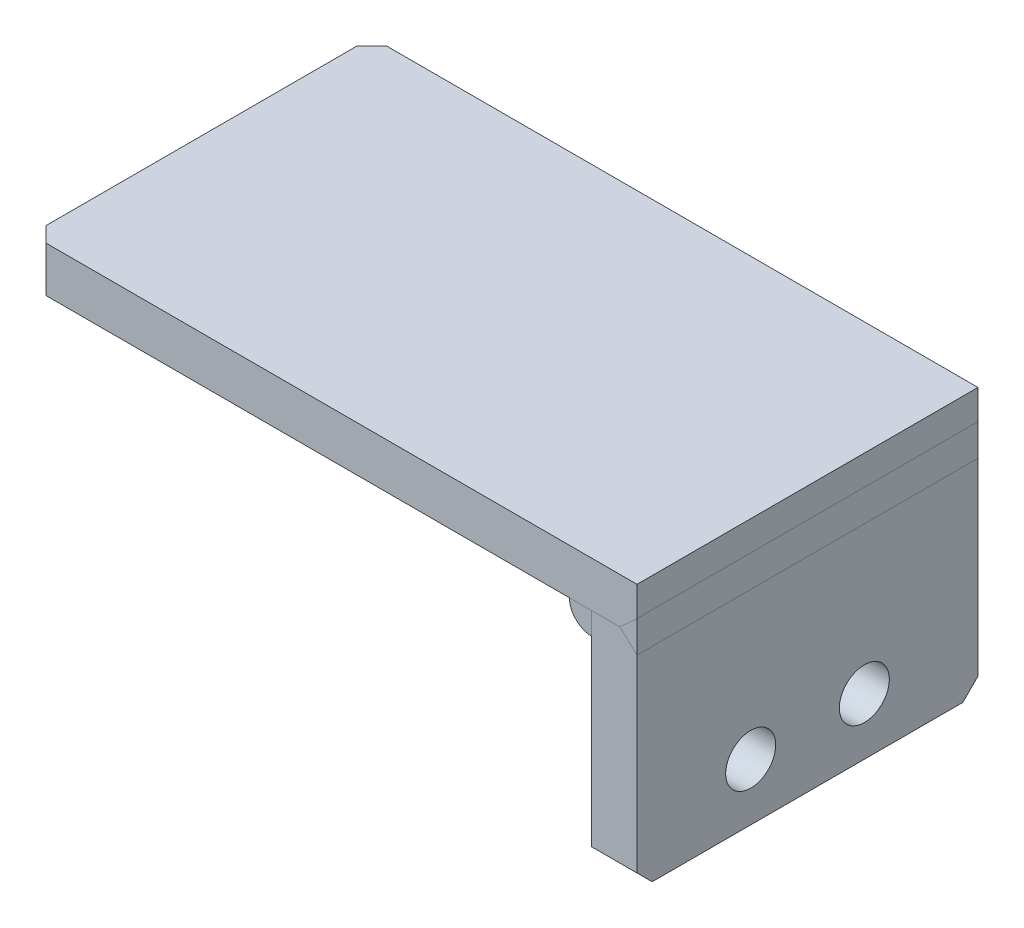
SolidWorks part; units mm, degrees
ref_plane "Front Plane" through (0, 0, 0) normal (0, 0, 1) x (1, 0, 0)
ref_plane "Top Plane" through (0, 0, 0) normal (0, 1, 0) x (1, 0, 0)
ref_plane "Right Plane" through (0, 0, 0) normal (1, 0, 0) x (0, 0, -1)
sketch "Sketch1" plane through (0, 0, 0) normal (0, 1, 0) x (1, 0, 0)
  line L1 (0, 0) -> (80, 0)
  line L2 (0, 0) -> (0, 45)
  line L3 (0, 45) -> (80, 45)
  line L4 (80, 0) -> (80, 45)
  point P4 (0, 0)
  dimension "D1" = 45
  dimension "D2" = 80
extrude "Boss-Extrude1" add sketch "Sketch1" against normal blind 6
chamfer "Chamfer1" distance 2 angle 45 2 edges at (0, -3, 0) (0, -3, -45)
sketch "Sketch2" plane through (0, -6, 0) normal (0, -1, 0) x (1, 0, 0)
  line L0 (80, -45) -> (2, -45) construction
  line L1 (80, 0) -> (74, 0)
  line L2 (80, 0) -> (80, -45)
  line L3 (80, -45) -> (74, -45)
  line L4 (74, 0) -> (74, -45)
  line L5 (2, 0) -> (80, 0) construction
  point P4 (0, 0)
  point P6 (0, 0)
  point P7 (0, 0)
  point P10 (0, 0)
  point P13 (72.2421, -43.4733)
  point P14 (0, 0)
  point P16 (65.5383, -45)
  dimension "D1" = 6
extrude "Boss-Extrude2" add sketch "Sketch2" along normal blind 29 separate body
sketch "Sketch4" plane through (0, 0, 0) normal (0, 0, 1) x (1, 0, 0)
  line L0 (74, -8.9199) -> (74, -6)
  line L1 (71.0801, -6) -> (74, -6)
  line L2 (80, -3.9063) -> (80, -8.0852)
  line L3 (80, -8.0852) -> (77.7328, -6)
  line L4 (77.7328, -6) -> (80, -3.9063)
  arc A0 (71.0801, -6) -> (74, -8.9199) centre (74, -6) ccw
  point P3 (78.4213, -6)
  point P5 (74, -7.4599)
  point P8 (72.5401, -6)
  point P9 (0, 0)
  point P11 (0, 0)
  point P12 (77.7328, -6)
extrude "Cut-Extrude1" cut sketch "Sketch4" against normal through all
extrude "Boss-Extrude3" add sketch "Sketch4<2>" against normal through all separate body
sketch "Sketch4<2>" plane through (0, 0, 0) normal (0, 0, 1) x (1, 0, 0) same geometry as "Sketch4"
sketch "Sketch6" plane through (80, 0, 0) normal (1, 0, 0) x (0, 0, -1)
  line L0 (0, 0) -> (45, 0) construction
  line L2 (45, -35) -> (45, -8.0852) construction
  circle A0 centre (15, -27.5) radius 3.3
  circle A1 centre (30, -27.5) radius 3.3
  point P4 (0, 0)
  point P5 (0, 0)
  point P8 (0, 0)
  point P9 (0, 0)
  point P12 (0, 0)
  dimension "D1" = 15
  dimension "D3" = 6.6
  dimension "D2" = 27.5
  dimension "D4" = 15
extrude "Cut-Extrude2" cut sketch "Sketch6" against normal through all
chamfer "Chamfer2" distance 2 angle 45 2 edges at (77, -35, -45) (77, -35, 0)
